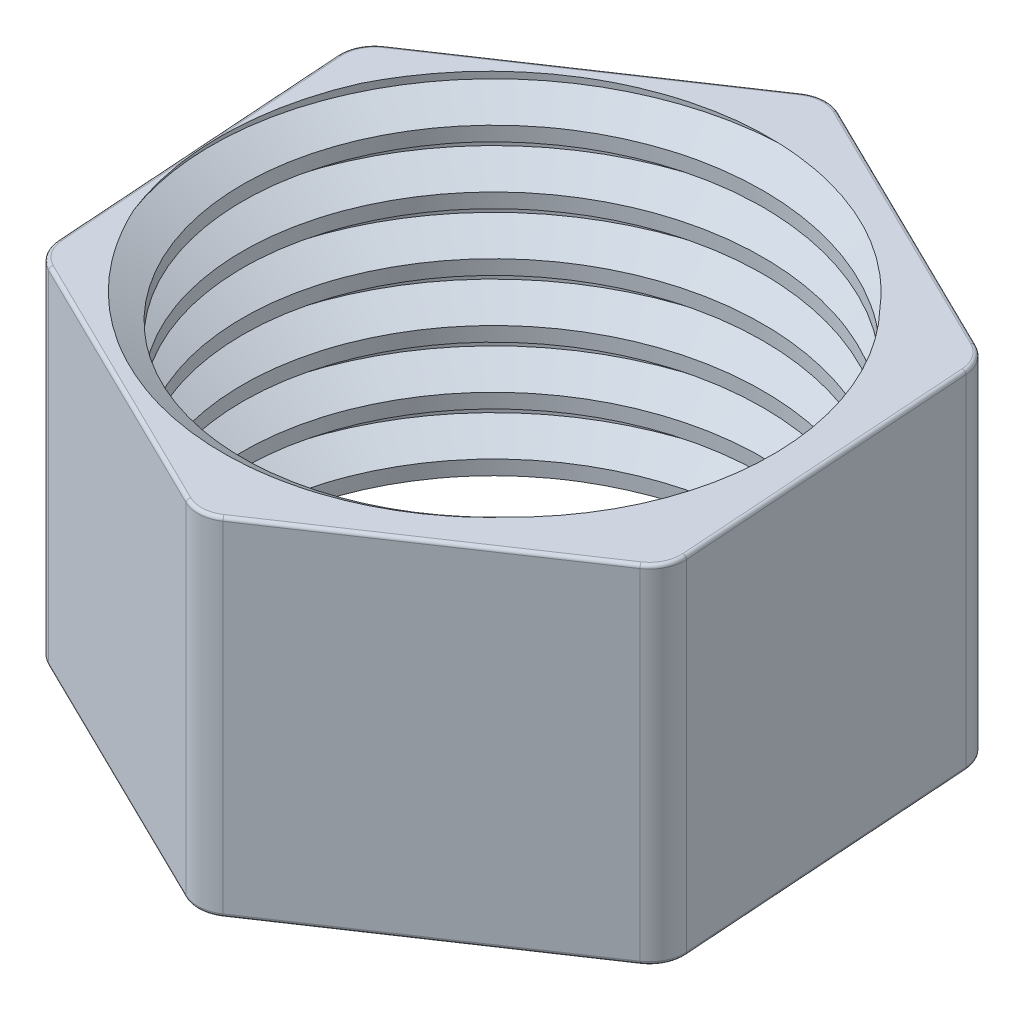
SolidWorks part; units mm, degrees
ref_plane "Front Plane" through (0, 0, 0) normal (0, 0, 1) x (1, 0, 0)
ref_plane "Top Plane" through (0, 0, 0) normal (0, 1, 0) x (1, 0, 0)
ref_plane "Right Plane" through (0, 0, 0) normal (1, 0, 0) x (0, 0, -1)
sketch "Sketch1" plane through (0, 0, 0) normal (0, 1, 0) x (1, 0, 0)
  line L1 (10.348, 6.9494) -> (-0.8443, 12.4364)
  line L2 (-0.8443, 12.4364) -> (-11.1924, 5.487)
  line L3 (-11.1924, 5.487) -> (-10.348, -6.9494)
  line L4 (-10.348, -6.9494) -> (0.8443, -12.4364)
  line L5 (0.8443, -12.4364) -> (11.1924, -5.487)
  line L6 (11.1924, -5.487) -> (10.348, 6.9494)
  circle A0 centre (0, 0) radius 9.525
  circle A1 centre (0, 0) radius 10.795 construction
  dimension "D1" = 19.05
  dimension "D2" = 21.59
extrude "Boss-Extrude1" add sketch "Sketch1" along normal mid plane 12.7
thread "Thread1" pitch 2.1167 method cut trim with start face yes trim with end face yes profile "Thread Profile1" start angle 0, offset 6.08, length 0, pitch 2.1167, diameter 19.05
ref_plane "Plane1" through (9.525, -12.43, 0) normal (0, 0, 1) x (1, 0, 0)
sketch "Thread Profile1" plane through (9.525, -12.43, 0) normal (0, 0, 1) x (1, 0, 0)
  line L0 (0, 0) -> (0, 2.1167) construction
  line L1 (0, 0) -> (1.1457, 0.6615)
  line L2 (1.1457, 0.6615) -> (1.1457, 0.926)
  line L3 (1.1457, 0.926) -> (0, 1.5875)
  line L4 (1.1457, 0.7937) -> (0, 0.7937) construction
  line L11 (0, 0) -> (0, 1.5875)
  point P2 (0, 0)
  dimension "Pitch" = 2.1167
  dimension "Profile_Angle" = 60
  dimension "Profile_Land" = 0.2646
  dimension "Profile_Height" = 1.1457
fillet "Fillet1" radius 1.27 6 edges at (-0.8443, 0, -12.4364) (-11.1924, 0, -5.487) (-10.348, 0, 6.9494) (0.8443, 0, 12.4364) (11.1924, 0, 5.487) (10.348, 0, -6.9494)
fillet "Fillet2" radius 0.127 24 edges at (10.1849, 6.35, -6.8399) (10.7702, 6.35, -0.7312) (11.016, 6.35, 5.4005) (6.0184, 6.35, 8.9617) (0.831, 6.35, 12.2403) (-4.7519, 6.35, 9.6929) (-10.1849, 6.35, 6.8399) (-11.016, 6.35, -5.4005) (-0.831, 6.35, -12.2403) (-10.1849, -6.35, 6.8399) (-11.016, -6.35, -5.4005) (-6.0184, -6.35, -8.9617) (-0.831, -6.35, -12.2403) (10.1849, -6.35, -6.8399) (10.7702, -6.35, -0.7312) (11.016, -6.35, 5.4005) (6.0184, -6.35, 8.9617) (0.831, -6.35, 12.2403) (4.7519, 6.35, -9.6929) (4.7519, -6.35, -9.6929) (-4.7519, -6.35, 9.6929) (-10.7702, 6.35, 0.7312) (-6.0184, 6.35, -8.9617) (-10.7702, -6.35, 0.7312)
